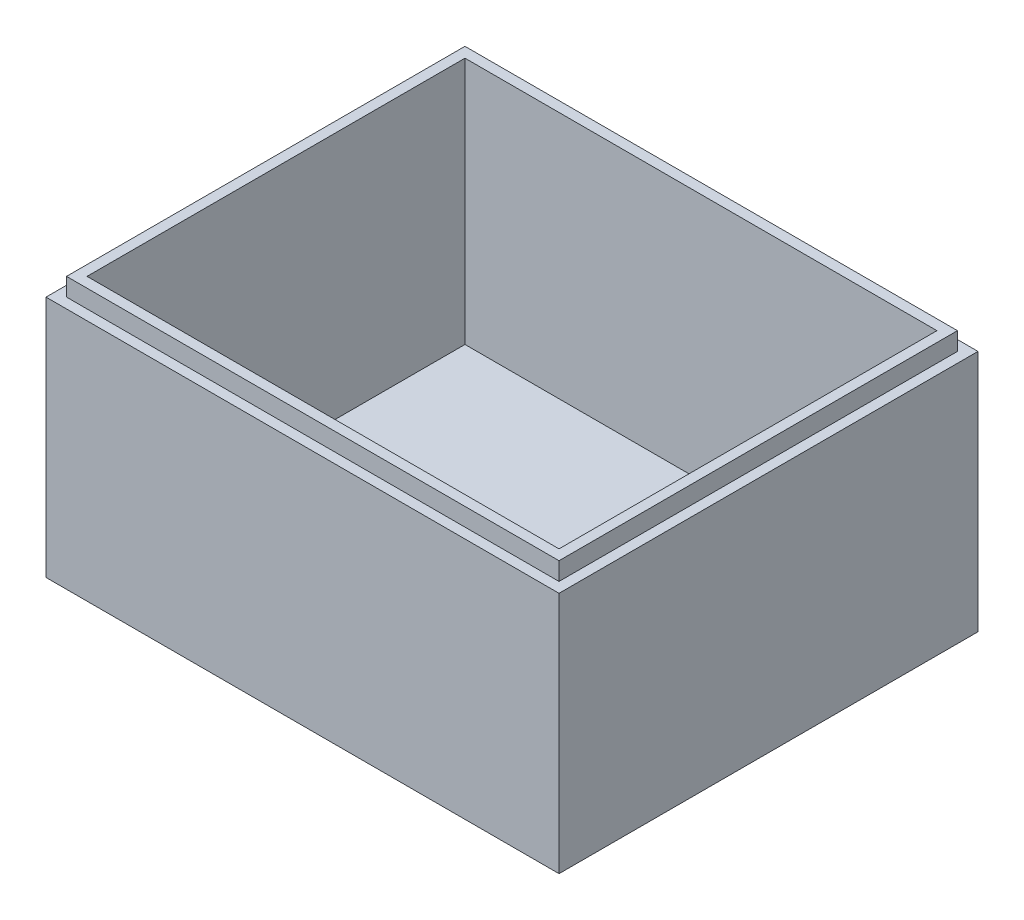
SolidWorks part; units mm, degrees
ref_plane "Front Plane" through (0, 0, 0) normal (0, 0, 1) x (1, 0, 0)
ref_plane "Top Plane" through (0, 0, 0) normal (0, 1, 0) x (1, 0, 0)
ref_plane "Right Plane" through (0, 0, 0) normal (1, 0, 0) x (0, 0, -1)
sketch "BatteryAndOuterWalls" plane through (0, 0, 0) normal (0, 1, 0) x (1, 0, 0)
  line L0 (30, -24.5) -> (30, 24.5)
  line L1 (27.6, -22.1) -> (-27.6, -22.1)
  line L2 (27.6, -22.1) -> (27.6, 22.1)
  line L3 (27.6, 22.1) -> (-27.6, 22.1)
  line L4 (-27.6, -22.1) -> (-27.6, 22.1)
  line L5 (27.6, -22.1) -> (-27.6, 22.1) construction
  line L6 (27.6, 22.1) -> (-27.6, -22.1) construction
  line L7 (30, 24.5) -> (-30, 24.5)
  line L8 (-30, -24.5) -> (-30, 24.5)
  line L9 (30, -24.5) -> (-30, -24.5)
  point P0 (0, 0)
  dimension "D1" = 55.2
  dimension "D2" = 44.2
  dimension "D4" = 60
  dimension "D5" = 49
  dimension "D3" = 2.4
extrude "Walls" add sketch "BatteryAndOuterWalls" along normal blind 29
sketch "SinkRim" plane through (0, 29, 0) normal (0, 1, 0) x (1, 0, 0)
  line L0 (-28.8, 23.3) -> (-28.8, -23.3)
  line L5 (-27.6, 22.1) -> (27.6, 22.1)
  line L6 (-27.6, 22.1) -> (-27.6, -22.1)
  line L7 (-27.6, -22.1) -> (27.6, -22.1)
  line L8 (27.6, 22.1) -> (27.6, -22.1)
  line L9 (-28.8, -23.3) -> (28.8, -23.3)
  line L10 (28.8, 23.3) -> (28.8, -23.3)
  line L11 (-28.8, 23.3) -> (28.8, 23.3)
  line L12 (-30, 24.5) -> (30, 24.5)
  line L13 (30, 24.5) -> (30, -24.5)
  line L14 (-30, -24.5) -> (30, -24.5)
  line L15 (-30, 24.5) -> (-30, -24.5)
  line M5 (-30, -24.5) -> (30, -24.5)
  line M6 (30, -24.5) -> (30, 24.5)
  line M7 (30, 24.5) -> (-30, 24.5)
  line M8 (-30, 24.5) -> (-30, -24.5)
  dimension "D1" = 1.2
  dimension "D2" = 1.2
sketch "Sketch2" plane through (0, 0, 0) normal (0, -1, 0) x (1, 0, 0)
  line L0 (-30, 24.5) -> (30, 24.5) construction
  line L5 (-30, 24.5) -> (30, 24.5)
  line L6 (-30, 24.5) -> (-30, -24.5)
  line L7 (-30, -24.5) -> (30, -24.5)
  line L8 (30, 24.5) -> (30, -24.5)
  line L9 (-30, -24.5) -> (-30, 24.5) construction
extrude "Bottom" add sketch "Sketch2" along normal blind 1.5
extrude "Top-Cut" cut sketch "SinkRim" against normal blind 2.1 contours L0 L11 L10 L9 M8 M5 M6 M7 region at (0, 29, -23.7253)
sketch "Sketch3" plane through (30, 0, 0) normal (1, 0, 0) x (0, 0, -1)
  line L0 (-24.5, 26.9) -> (-24.5, -1.5) construction
  line L1 (-22.1, 29) -> (22.1, 29)
  line L2 (-22.1, 29) -> (-22.1, 0)
  line L3 (-22.1, 0) -> (22.1, 0)
  line L4 (22.1, 29) -> (22.1, 0)
  line L5 (24.5, -1.5) -> (-24.5, -1.5) construction
  line L6 (24.5, 26.9) -> (24.5, -1.5) construction
  line L7 (23.3, 29) -> (-23.3, 29) construction
  dimension "D1" = 2.4
  dimension "D2" = 1.5
  dimension "D3" = 2.4
  dimension "D4" = 0
